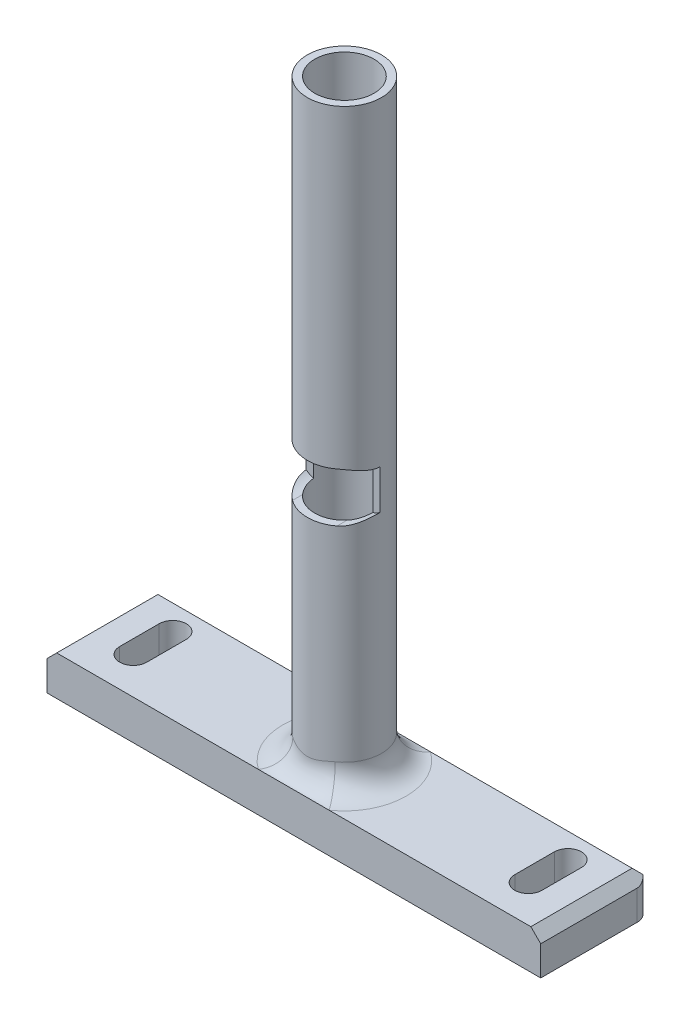
SolidWorks part; units mm, degrees
ref_plane "Front Plane" through (0, 0, 0) normal (0, 0, 1) x (1, 0, 0)
ref_plane "Top Plane" through (0, 0, 0) normal (0, 1, 0) x (1, 0, 0)
ref_plane "Right Plane" through (0, 0, 0) normal (1, 0, 0) x (0, 0, -1)
sketch "Sketch1" plane through (0, 0, 0) normal (0, 1, 0) x (1, 0, 0)
  line L0 (40, 23) -> (40, 15) construction
  line L1 (-50, 30) -> (50, 30)
  line L2 (-50, 30) -> (-50, -30)
  line L3 (-50, -30) -> (50, -30)
  line L4 (50, 30) -> (50, -30)
  line L5 (-15, -7.5) -> (15, -7.5)
  line L6 (-15, -7.5) -> (-15, 7.5)
  line L7 (-15, 7.5) -> (15, 7.5)
  line L8 (15, -7.5) -> (15, 7.5)
  line L9 (-15, -7.5) -> (15, 7.5) construction
  line L10 (-15, 7.5) -> (15, -7.5) construction
  line L11 (42.75, 23) -> (42.75, 15)
  line L12 (37.25, 23) -> (37.25, 15)
  line L13 (40, -23) -> (40, -15) construction
  line L14 (37.25, -23) -> (37.25, -15)
  line L15 (42.75, -23) -> (42.75, -15)
  line L16 (-40, -15) -> (-40, -23) construction
  line L17 (-37.25, -15) -> (-37.25, -23)
  line L18 (-42.75, -15) -> (-42.75, -23)
  line L19 (-40, 23) -> (-40, 15) construction
  line L20 (-37.25, 23) -> (-37.25, 15)
  line L21 (-42.75, 23) -> (-42.75, 15)
  line L22 (-30, -26.25) -> (-30, -10.81) construction
  line L23 (-21.5, -30) -> (21.5, -30)
  line L24 (-21.5, -30) -> (-21.5, -21)
  line L25 (-21.5, -21) -> (21.5, -21)
  line L26 (21.5, -30) -> (21.5, -21)
  line L27 (11.5, -21) -> (-11.5, -21)
  line L28 (11.5, -21) -> (11.5, -18.5)
  line L29 (11.5, -18.5) -> (-11.5, -18.5)
  line L30 (-11.5, -21) -> (-11.5, -18.5)
  line L31 (-31.75, -26.25) -> (-31.75, -10.81)
  line L32 (-28.25, -26.25) -> (-28.25, -10.81)
  line L33 (30, -10.81) -> (30, -26.25) construction
  line L34 (31.75, -10.81) -> (31.75, -26.25)
  line L35 (28.25, -10.81) -> (28.25, -26.25)
  line L37 (13, -21) -> (18, -21)
  line L38 (13, -21) -> (13, -15.5)
  line L39 (13, -15.5) -> (18, -15.5)
  line L40 (18, -21) -> (18, -15.5)
  line L41 (-13, -21) -> (-18, -21)
  line L42 (-13, -21) -> (-13, -15.5)
  line L43 (-13, -15.5) -> (-18, -15.5)
  line L44 (-18, -21) -> (-18, -15.5)
  circle A0 centre (-40, 19) radius 2.75
  circle A1 centre (-40, 19) radius 11.95 construction
  circle A2 centre (40, 19) radius 2.75
  circle A3 centre (-40, -19) radius 2.75
  circle A4 centre (40, -19) radius 2.75
  arc A5 (42.75, 23) -> (37.25, 23) centre (40, 23) ccw
  arc A6 (37.25, 15) -> (42.75, 15) centre (40, 15) ccw
  arc A7 (37.25, -23) -> (42.75, -23) centre (40, -23) ccw
  arc A8 (42.75, -15) -> (37.25, -15) centre (40, -15) ccw
  arc A9 (-37.25, -15) -> (-42.75, -15) centre (-40, -15) ccw
  arc A10 (-42.75, -23) -> (-37.25, -23) centre (-40, -23) ccw
  arc A11 (-37.25, 23) -> (-42.75, 23) centre (-40, 23) ccw
  arc A12 (-42.75, 15) -> (-37.25, 15) centre (-40, 15) ccw
  arc A13 (-31.75, -26.25) -> (-28.25, -26.25) centre (-30, -26.25) ccw
  arc A14 (-28.25, -10.81) -> (-31.75, -10.81) centre (-30, -10.81) ccw
  arc A15 (31.75, -10.81) -> (28.25, -10.81) centre (30, -10.81) ccw
  arc A16 (28.25, -26.25) -> (31.75, -26.25) centre (30, -26.25) ccw
  point P14 (0, 0)
  point P21 (40, 19)
  point P28 (40, -19)
  point P35 (-40, -19)
  point P42 (-40, 19)
  point P51 (0, -21)
  point P56 (0, -18.5)
  point P59 (-30, -18.53)
  point P66 (30, -18.53)
  dimension "D5" = 5.5
  dimension "D8" = 23.9
  dimension "D9" = 5.5
  dimension "D10" = 10
  dimension "D12" = 5.5
  dimension "D13" = 11
  dimension "D14" = 10
  dimension "D15" = 11
  dimension "D16" = 5.5
  dimension "D33" = 10
  dimension "D1" = 60
  dimension "D2" = 100
  dimension "D3" = 50
  dimension "D4" = 30
  dimension "D6" = 10
  dimension "D7" = 11
  dimension "D11" = 11
  dimension "10" = 10
  dimension "D17" = 15
  dimension "D18" = 30
  dimension "D19" = 5.5
  dimension "D20" = 8
  dimension "D21" = 5.5
  dimension "D22" = 8
  dimension "D23" = 5.5
  dimension "D24" = 8
  dimension "D25" = 5.5
  dimension "D26" = 8
  dimension "D27" = 43
  dimension "D28" = 9
  dimension "D29" = 2.5
  dimension "D30" = 23
  dimension "D31" = 3.5
  dimension "D32" = 15.44
  dimension "D34" = 3.75
  dimension "D35" = 3.5
  dimension "D36" = 15.44
  dimension "D37" = 10
  dimension "D38" = 3.75
  dimension "D39" = 13
  dimension "D40" = 5
  dimension "D41" = 5.5
  dimension "D42" = 5
  dimension "D43" = 13
  dimension "D44" = 5.5
sketch "Sketch2" plane through (0, 0, 0) normal (0, 1, 0) x (1, 0, 0)
  line L0 (-100, -10) -> (100, 10) construction
  line L1 (-100, 10) -> (100, 10) construction
  line L2 (-100, 10) -> (-100, -10) construction
  line L3 (-100, -10) -> (100, -10) construction
  line L4 (100, 10) -> (100, -10) construction
  dimension "D1" = 200
  dimension "D2" = 20
extrude "Boss-Extrude1" add sketch "Sketch1" along normal blind 8 contours L4 L1 L2 L3 A12 L21 A11 L20 A10 L18 A9 L17 A8 L15 A7 L14 A6 L12 A5 L11 L8 L5 L6 L7
sketch "Sketch4" plane through (0, 0, 18.5) normal (0, 0, 1) x (1, 0, 0)
  line L0 (11.5, 8) -> (-11.5, 8) construction
  circle A0 centre (0, 8) radius 6.45
  dimension "D1" = 12.9
extrude "Cut-Extrude1" cut sketch "Sketch4" against normal up to surface (11 mm away) up to face at (0, 4, 7.5)
sketch "Sketch5" plane through (0, 0, 21) normal (0, 0, 1) x (1, 0, 0)
  line L0 (13, 5.2) -> (11.5, 1.5)
  line L2 (11.5, 8) -> (11.5, 0) construction
  line L3 (18, 2) -> (19.75, 0)
  line L4 (18, 8) -> (18, 0) construction
  line L5 (18, 0) -> (21.5, 0) construction
  line L6 (21.5, 0) -> (21.5, 8) construction
  line L7 (21.5, 8) -> (18, 8) construction
  line L8 (11.5, 0) -> (13, 0) construction
  line L9 (13, 0) -> (13, 8) construction
  line L10 (13, 8) -> (11.5, 8) construction
  line L11 (18, 0) -> (21.5, 0)
  line L12 (21.5, 0) -> (21.5, 8)
  line L13 (21.5, 8) -> (18, 8)
  line L14 (18, 8) -> (18, 0)
  line L15 (11.5, 0) -> (13, 0)
  line L16 (13, 0) -> (13, 8)
  line L17 (13, 8) -> (11.5, 8)
  line L18 (11.5, 8) -> (11.5, 0)
  line L19 (13, 8) -> (13, 0) construction
  line L21 (-21.5, 0) -> (-18, 0) construction
  line L22 (-18, 0) -> (-18, 8) construction
  line L23 (-18, 8) -> (-21.5, 8) construction
  line L24 (-21.5, 8) -> (-21.5, 0) construction
  line L25 (-13, 0) -> (-11.5, 0) construction
  line L26 (-11.5, 0) -> (-11.5, 8) construction
  line L27 (-11.5, 8) -> (-13, 8) construction
  line L28 (-13, 8) -> (-13, 0) construction
  line L29 (-21.5, 0) -> (-18, 0)
  line L30 (-18, 0) -> (-18, 8)
  line L31 (-18, 8) -> (-21.5, 8)
  line L32 (-21.5, 8) -> (-21.5, 0)
  line L33 (-13, 0) -> (-11.5, 0)
  line L34 (-11.5, 0) -> (-11.5, 8)
  line L35 (-11.5, 8) -> (-13, 8)
  line L36 (-13, 8) -> (-13, 0)
  line L37 (-13, 5.2) -> (-11.5, 1.5)
  line L38 (-18, 2) -> (-19.75, 0)
  line L39 (11.5, 1.5) -> (10.5, 0)
  line L40 (-11.5, 1.5) -> (-10.5, 0)
  line L44 (-6.45, 8) -> (-11.5, 8)
  line L45 (-11.5, 8) -> (-11.5, 0)
  line L46 (-11.5, 0) -> (11.5, 0)
  line L47 (11.5, 0) -> (11.5, 8)
  line L48 (11.5, 8) -> (6.45, 8)
  line L49 (-6.45, 8) -> (-11.5, 8)
  line L50 (-11.5, 8) -> (-11.5, 0)
  line L51 (-11.5, 0) -> (11.5, 0)
  line L52 (11.5, 0) -> (11.5, 8)
  line L53 (11.5, 8) -> (6.45, 8)
  arc A1 (-6.45, 8) -> (6.45, 8) centre (0, 8) ccw
  arc A2 (-6.45, 8) -> (6.45, 8) centre (0, 8) ccw
  line M1 (18, 0) -> (21.5, 0)
  line M4 (18, 8) -> (18, 0)
  dimension "D1" = 1.5
  dimension "D2" = 2
  dimension "D3" = 5.2
  dimension "D4" = 5.2
  dimension "D5" = 1.5
  dimension "D6" = 2
  dimension "D8" = 1
  dimension "D9" = 1
  dimension "D7" = 0
extrude "Cut-Extrude2" cut sketch "Sketch5" against normal up to surface (5.5 mm away) contours L0 L18 L15 L16 | L3 M4 M1 | L37 L36 L33 L34 | L30 L38 L29 | L39 L51 L18 | L34 L51 L40 up to face at (15.5, 4, 15.5)
chamfer "Chamfer1" distance 2 angle 45 3 edges at (50, 8, 0) (0, 8, -30) (-50, 8, 0)
fillet "Fillet1" radius 3 4 edges at (-50, 3, 30) (50, 3, 30) (50, 3, -30) (-50, 3, -30)
sketch "Sketch7" plane through (0, 8, 0) normal (0, 1, 0) x (1, 0, 0)
  line L0 (15, 7.5) -> (15, 28) construction
  line L1 (-15, 7.5) -> (15, 7.5) construction
  line L2 (15, -7.5) -> (15, 7.5) construction
  line L3 (48, 28) -> (-48, 28) construction
  line L4 (-15, 7.5) -> (-15, 28) construction
  line L5 (15, 28) -> (-15, 7.5) construction
  line L6 (15, 7.5) -> (-15, 28) construction
  circle A0 centre (0, 17.75) radius 7.5
  circle A1 centre (0, 17.75) radius 6
  dimension "D1" = 12
  dimension "D2" = 15
extrude "Boss-Extrude3" add sketch "Sketch7" along normal blind 120
fillet "Fillet2" radius 5 1 edges at (0, 8, -10.25)
ref_plane "Plane1" through (0, 0, -7.5) normal (0, 0, 1) x (1, 0, 0)
split "Split1" trim tools "Plane1" bodies to split 105 resulting bodies 106 107
split "Split2" trim tools "Plane1" bodies to split 107 106 resulting bodies 108 109
delete or keep bodies "Body-Delete/Keep 1" type delete bodies bodies 108
sketch "Sketch12" plane through (0, 0, -7.5) normal (0, 0, 1) x (1, 0, 0)
  line L0 (0, 128) -> (0, -9.2433) construction
  line L1 (7.5, 128) -> (-7.5, 128) construction
  line L2 (4.5, 59.3783) -> (-4.5, 59.3783) construction
  line L3 (4.5, 54.3783) -> (-4.5, 54.3783)
  line L4 (4.5, 64.3783) -> (-4.5, 64.3783)
  arc A0 (4.5, 54.3783) -> (4.5, 64.3783) centre (4.5, 59.3783) ccw
  arc A1 (-4.5, 64.3783) -> (-4.5, 54.3783) centre (-4.5, 59.3783) ccw
  point P7 (0, 59.3783)
extrude "Cut-Extrude3" cut sketch "Sketch12" against normal blind 10
